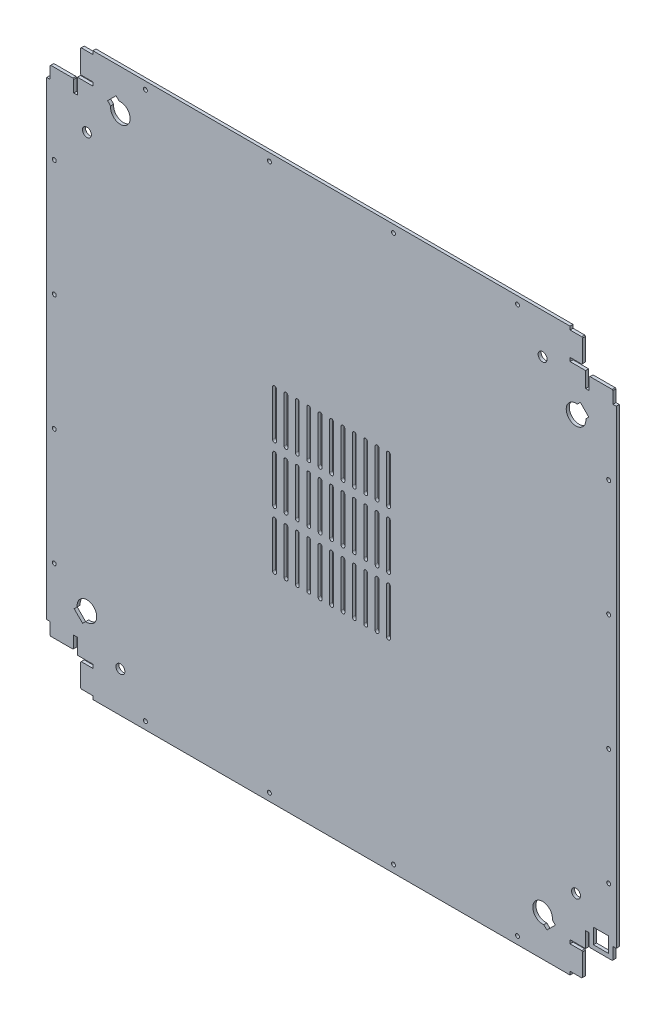
SolidWorks part; units mm, degrees
material "PC Высокая вязкость"
ref_plane "Спереди" through (0, 0, 0) normal (0, 0, 1) x (1, 0, 0)
ref_plane "Сверху" through (0, 0, 0) normal (0, 1, 0) x (1, 0, 0)
ref_plane "Справа" through (0, 0, 0) normal (1, 0, 0) x (0, 0, -1)
sketch "Эскиз1" plane through (0, 0, 0) normal (0, 0, 1) x (1, 0, 0)
  line L1 (375, -370) -> (-375, -370)
  line L2 (375, -370) -> (375, 370)
  line L3 (375, 370) -> (-375, 370)
  line L4 (-375, -370) -> (-375, 370)
  point P1 (375, 0)
  point P2 (0, 370)
  dimension "D1" = 740
  dimension "D2" = 750
extrude "Бобышка-Вытянуть1" add sketch "Эскиз1" along normal blind 4
sketch "Эскиз11" plane through (0, 0, 4) normal (0, 0, 1) x (1, 0, 0)
  line L0 (-375, 370) -> (-375, -370) construction
  line L1 (-375, -370) -> (375, -370) construction
  line L2 (-365, -240) -> (-365, -86.67) construction
  line L3 (-245, -360) -> (-81.67, -360) construction
  line L4 (-375, 370) -> (-375, -370) construction
  line L5 (0, 0) -> (0, 50000) construction
  line L6 (0, 0) -> (-50000, 0) construction
  line L9 (0, 0) -> (50000, 0) construction
  line L10 (365, -240) -> (365, -86.67) construction
  circle A0 centre (-365, -240) radius 2.6
  circle A10 centre (-245, -360) radius 2.6
  circle A25 centre (-365, -86.67) radius 2.6
  circle A26 centre (-365, 66.66) radius 2.6
  circle A27 centre (-365, 219.99) radius 2.6
  circle A28 centre (-81.67, -360) radius 2.6
  circle A29 centre (81.66, -360) radius 2.6
  circle A30 centre (244.99, -360) radius 2.6
  circle A31 centre (365, 219.99) radius 2.6
  circle A32 centre (365, 66.66) radius 2.6
  circle A33 centre (365, -86.67) radius 2.6
  circle A34 centre (365, -240) radius 2.6
  circle A35 centre (-245, 360) radius 2.6
  circle A36 centre (-81.67, 360) radius 2.6
  circle A37 centre (81.66, 360) radius 2.6
  circle A38 centre (244.99, 360) radius 2.6
  dimension "D1" = 5.2
  dimension "D3" = 130
  dimension "D6" = 10
  dimension "D2" = 10
  dimension "D5" = 153.33
  dimension "D7" = 130
  dimension "D9" = 163.33
  dimension "D4" = 4
  dimension "D8" = 4
extrude "Вырез-Вытянуть4" cut sketch "Эскиз11" against normal through all
sketch "Эскиз6" plane through (0, 0, 4) normal (0, 0, 1) x (1, 0, 0)
  line L0 (0, 5) -> (375, -370) construction
  line L1 (-375, -370) -> (375, -370) construction
  line L2 (375, -370) -> (375, 370) construction
  line L3 (-375, -370) -> (0, 5) construction
  line L7 (-375, 370) -> (-5, 0) construction
  line L8 (-5, 0) -> (-375, -370) construction
  circle A0 centre (0, 5) radius 530.3301 construction
  circle A1 centre (265, -360) radius 2.75 construction
  circle A3 centre (-5, 0) radius 523.259 construction
  point P0 (0, 5)
  point P1 (-5, 0)
  point P11 (-375, -370)
  dimension "D3" = 1060.6602
  dimension "D4" = 5.5
  dimension "D11" = 1046.518
  dimension "D1" = 0
  dimension "D2" = 5
  dimension "D5" = 10
  dimension "D6" = 110
  dimension "D7" = 90
  dimension "D12" = 90
  dimension "D13" = 5
sketch "Эскиз9" plane through (0, 0, 4) normal (0, 0, 1) x (1, 0, 0)
  line L55 (-375, -309.1) -> (-370.6, -309.1)
  line L56 (-375, 370) -> (-375, -370) construction
  line L57 (-370.6, -309.1) -> (-370.6, -324.6)
  line L58 (-369.6, -325.6) -> (-340.4, -325.6)
  line L59 (-339.4, -324.6) -> (-339.4, -309.1)
  line L60 (-339.4, -309.1) -> (-334.6, -309.1)
  line L61 (-334.6, -309.1) -> (-334.6, -329.6)
  line L62 (-314.1, -370) -> (-314.1, -365.6)
  line L63 (-375, -370) -> (375, -370) construction
  line L64 (-314.1, -365.6) -> (-329.6, -365.6)
  line L65 (-330.6, -364.6) -> (-330.6, -335.4)
  line L66 (-329.6, -334.4) -> (-314.1, -334.4)
  line L67 (-314.1, -334.4) -> (-314.1, -329.6)
  line L68 (-314.1, -329.6) -> (-334.6, -329.6)
  line L71 (-375, 370) -> (-375, -370) construction
  line L72 (-375, -329.5) -> (-337, -329.5) construction
  line L100 (-375, -309.1) -> (-375, -370)
  line L101 (-375, -370) -> (-335, -370) construction
  line L102 (-375, -370) -> (-375, -330) construction
  line L103 (-375, -330) -> (-335, -330) construction
  line L104 (-335, -370) -> (-335, -330) construction
  line L105 (-375, -370) -> (-314.1, -370)
  line L106 (-370.6, -324.6) -> (-369.6, -325.6)
  line L107 (-340.4, -325.6) -> (-339.4, -324.6)
  line L108 (-330.6, -335.4) -> (-329.6, -334.4)
  line L109 (-329.6, -365.6) -> (-330.6, -364.6)
  point P8 (-370.6, -325.6)
  point P9 (-339.4, -325.6)
  point P17 (-330.6, -334.4)
  point P18 (-330.6, -365.6)
  dimension "D2" = 4.4
  dimension "D1" = 40
  dimension "D3" = 4.4
  dimension "D4" = 4.4
  dimension "D5" = 4.8
  dimension "D6" = 16.5
  dimension "D7" = 40.4
  dimension "D8" = 40.4
extrude "Вырез-Вытянуть3" cut sketch "Эскиз9" against normal through all
sketch "Эскиз5" plane through (0, 0, 0) normal (0, 0, -1) x (-1, 0, 0)
  line L0 (314.1, -370) -> (-375, -370) construction
  line L1 (375, 370) -> (375, -309.1) construction
  line L9 (323.625, -285.7972) -> (327.6569, -289.8291)
  line L11 (318.6, -269.6) -> (35673.9391, -35624.9391) construction
  line L13 (278.5162, -316.4838) -> (35633.8552, 35038.8552) construction
  line L14 (327.6569, -289.8291) -> (338.8291, -278.6569)
  line L15 (338.8291, -278.6569) -> (334.7972, -274.625)
  line L21 (327.6569, -289.2635) -> (338.2635, -278.6569) construction
  line L22 (323.7678, -285.3744) -> (327.6569, -289.2635) construction
  line L23 (338.2635, -278.6569) -> (334.3744, -274.7678) construction
  line L47 (265.1, -329.9) -> (290.9, -304.1) construction
  arc A4 (334.3744, -274.7678) -> (323.7678, -285.3744) centre (322, -273) ccw construction
  arc A5 (334.7972, -274.625) -> (323.625, -285.7972) centre (322, -273) ccw
  circle A6 centre (278, -317) radius 5.9
  circle A8 centre (278, -317) radius 5.5 construction
  point P10 (0, 26.0871)
  dimension "D4" = 5.5
  dimension "D6" = 0.4
  dimension "D7" = 11
  dimension "D5" = 0.4
  dimension "D10" = 12.9
  dimension "D11" = 12.9
  dimension "D14" = 12.9
  dimension "D15" = 12.9
  dimension "D16" = 97
  dimension "D17" = 53
  dimension "D18" = 53
  dimension "D28" = 7.5
  dimension "D29" = 7.5
  dimension "D30" = 15.5
  dimension "D31" = 97
  dimension "D32" = 135
extrude "Вырез-Вытянуть1" cut sketch "Эскиз5" against normal through all
ref_axis "Ось2" through (0, 5, 4) along (0, 0, 1)
ref_axis "Ось3" through (-5, 0, 4) along (0, 0, 1)
ref_axis "Ось4" through (0, 0, 0) along (0, 0, 1)
pattern_circular "Круговой массив2" count 2 every 90 about axis through (0, 5, 4) along (0, 0, 1) of "Вырез-Вытянуть1", "Вырез-Вытянуть3"
pattern_circular "Круговой массив3" count 2 every 90 about axis through (-5, 0, 4) along (0, 0, 1) of "Вырез-Вытянуть1", "Вырез-Вытянуть3" reverse direction yes
pattern_circular "Круговой массив4" count 2 over 360 about axis through (0, 0, 0) along (0, 0, 1) of "Вырез-Вытянуть1", "Вырез-Вытянуть3"
sketch "Эскиз12" plane through (0, 0, 4) normal (0, 0, 1) x (1, 0, 0)
  line L0 (375, -309.1) -> (375, 309.1) construction
  line L1 (365, -300) -> (345, -300)
  line L2 (365, -300) -> (365, -320)
  line L3 (365, -320) -> (345, -320)
  line L4 (345, -300) -> (345, -320)
  line L5 (369.6, -325.6) -> (340.4, -325.6) construction
  dimension "D1" = 20
  dimension "D2" = 10
  dimension "D3" = 5.6
extrude "Вырез-Вытянуть5" cut sketch "Эскиз12" against normal through all
sketch "Эскиз15" plane through (0, 0, 0) normal (0, 0, -1) x (-1, 0, 0)
  line L0 (-72.5, -105) -> (-72.5, -45)
  line L1 (-77.5, -45) -> (-77.5, -105)
  line L2 (-57.5, -105) -> (-57.5, -45)
  line L3 (-62.5, -45) -> (-62.5, -105)
  line L4 (-42.5, -105) -> (-42.5, -45)
  line L5 (-47.5, -45) -> (-47.5, -105)
  line L6 (-27.5, -105) -> (-27.5, -45)
  line L7 (-32.5, -45) -> (-32.5, -105)
  line L8 (-12.5, -105) -> (-12.5, -45)
  line L9 (-17.5, -45) -> (-17.5, -105)
  line L10 (2.5, -105) -> (2.5, -45)
  line L11 (-2.5, -45) -> (-2.5, -105)
  line L12 (17.5, -105) -> (17.5, -45)
  line L13 (12.5, -45) -> (12.5, -105)
  line L14 (32.5, -105) -> (32.5, -45)
  line L15 (27.5, -45) -> (27.5, -105)
  line L16 (47.5, -105) -> (47.5, -45)
  line L17 (42.5, -45) -> (42.5, -105)
  line L18 (62.5, -105) -> (62.5, -45)
  line L19 (57.5, -45) -> (57.5, -105)
  line L20 (77.5, -105) -> (77.5, -45)
  line L21 (72.5, -45) -> (72.5, -105)
  line L22 (-57.5, -30) -> (-57.5, 30)
  line L23 (-62.5, 30) -> (-62.5, -30)
  line L24 (-42.5, -30) -> (-42.5, 30)
  line L25 (-47.5, 30) -> (-47.5, -30)
  line L26 (-27.5, -30) -> (-27.5, 30)
  line L27 (-32.5, 30) -> (-32.5, -30)
  line L28 (-12.5, -30) -> (-12.5, 30)
  line L29 (-17.5, 30) -> (-17.5, -30)
  line L30 (2.5, -30) -> (2.5, 30)
  line L31 (-2.5, 30) -> (-2.5, -30)
  line L32 (17.5, -30) -> (17.5, 30)
  line L33 (12.5, 30) -> (12.5, -30)
  line L34 (32.5, -30) -> (32.5, 30)
  line L35 (27.5, 30) -> (27.5, -30)
  line L36 (47.5, -30) -> (47.5, 30)
  line L37 (42.5, 30) -> (42.5, -30)
  line L38 (62.5, -30) -> (62.5, 30)
  line L39 (57.5, 30) -> (57.5, -30)
  line L40 (77.5, -30) -> (77.5, 30)
  line L41 (72.5, 30) -> (72.5, -30)
  line L42 (-57.5, 45) -> (-57.5, 105)
  line L43 (-62.5, 105) -> (-62.5, 45)
  line L44 (-42.5, 45) -> (-42.5, 105)
  line L45 (-47.5, 105) -> (-47.5, 45)
  line L46 (-27.5, 45) -> (-27.5, 105)
  line L47 (-32.5, 105) -> (-32.5, 45)
  line L48 (-12.5, 45) -> (-12.5, 105)
  line L49 (-17.5, 105) -> (-17.5, 45)
  line L50 (2.5, 45) -> (2.5, 105)
  line L51 (-2.5, 105) -> (-2.5, 45)
  line L52 (17.5, 45) -> (17.5, 105)
  line L53 (12.5, 105) -> (12.5, 45)
  line L54 (32.5, 45) -> (32.5, 105)
  line L55 (27.5, 105) -> (27.5, 45)
  line L56 (47.5, 45) -> (47.5, 105)
  line L57 (42.5, 105) -> (42.5, 45)
  line L58 (62.5, 45) -> (62.5, 105)
  line L59 (57.5, 105) -> (57.5, 45)
  line L60 (77.5, 45) -> (77.5, 105)
  line L61 (72.5, 105) -> (72.5, 45)
  line L62 (-72.5, -30) -> (-72.5, 30)
  line L63 (-77.5, 30) -> (-77.5, -30)
  line L64 (-72.5, 45) -> (-72.5, 105)
  line L65 (-77.5, 105) -> (-77.5, 45)
  line L66 (-72.5, -105) -> (-57.5, -105) construction
  line L67 (-72.5, -105) -> (-72.5, -30) construction
  arc A0 (-77.5, -105) -> (-72.5, -105) centre (-75, -105) ccw
  arc A1 (-72.5, -45) -> (-77.5, -45) centre (-75, -45) ccw
  arc A2 (-57.5, -45) -> (-62.5, -45) centre (-60, -45) ccw
  arc A3 (-62.5, -105) -> (-57.5, -105) centre (-60, -105) ccw
  arc A4 (-42.5, -45) -> (-47.5, -45) centre (-45, -45) ccw
  arc A5 (-47.5, -105) -> (-42.5, -105) centre (-45, -105) ccw
  arc A6 (-27.5, -45) -> (-32.5, -45) centre (-30, -45) ccw
  arc A7 (-32.5, -105) -> (-27.5, -105) centre (-30, -105) ccw
  arc A8 (-12.5, -45) -> (-17.5, -45) centre (-15, -45) ccw
  arc A9 (-17.5, -105) -> (-12.5, -105) centre (-15, -105) ccw
  arc A10 (2.5, -45) -> (-2.5, -45) centre (0, -45) ccw
  arc A11 (-2.5, -105) -> (2.5, -105) centre (0, -105) ccw
  arc A12 (17.5, -45) -> (12.5, -45) centre (15, -45) ccw
  arc A13 (12.5, -105) -> (17.5, -105) centre (15, -105) ccw
  arc A14 (32.5, -45) -> (27.5, -45) centre (30, -45) ccw
  arc A15 (27.5, -105) -> (32.5, -105) centre (30, -105) ccw
  arc A16 (47.5, -45) -> (42.5, -45) centre (45, -45) ccw
  arc A17 (42.5, -105) -> (47.5, -105) centre (45, -105) ccw
  arc A18 (62.5, -45) -> (57.5, -45) centre (60, -45) ccw
  arc A19 (57.5, -105) -> (62.5, -105) centre (60, -105) ccw
  arc A20 (77.5, -45) -> (72.5, -45) centre (75, -45) ccw
  arc A21 (72.5, -105) -> (77.5, -105) centre (75, -105) ccw
  arc A22 (-57.5, 30) -> (-62.5, 30) centre (-60, 30) ccw
  arc A23 (-62.5, -30) -> (-57.5, -30) centre (-60, -30) ccw
  arc A24 (-42.5, 30) -> (-47.5, 30) centre (-45, 30) ccw
  arc A25 (-47.5, -30) -> (-42.5, -30) centre (-45, -30) ccw
  arc A26 (-27.5, 30) -> (-32.5, 30) centre (-30, 30) ccw
  arc A27 (-32.5, -30) -> (-27.5, -30) centre (-30, -30) ccw
  arc A28 (-12.5, 30) -> (-17.5, 30) centre (-15, 30) ccw
  arc A29 (-17.5, -30) -> (-12.5, -30) centre (-15, -30) ccw
  arc A30 (2.5, 30) -> (-2.5, 30) centre (0, 30) ccw
  arc A31 (-2.5, -30) -> (2.5, -30) centre (0, -30) ccw
  arc A32 (17.5, 30) -> (12.5, 30) centre (15, 30) ccw
  arc A33 (12.5, -30) -> (17.5, -30) centre (15, -30) ccw
  arc A34 (32.5, 30) -> (27.5, 30) centre (30, 30) ccw
  arc A35 (27.5, -30) -> (32.5, -30) centre (30, -30) ccw
  arc A36 (47.5, 30) -> (42.5, 30) centre (45, 30) ccw
  arc A37 (42.5, -30) -> (47.5, -30) centre (45, -30) ccw
  arc A38 (62.5, 30) -> (57.5, 30) centre (60, 30) ccw
  arc A39 (57.5, -30) -> (62.5, -30) centre (60, -30) ccw
  arc A40 (77.5, 30) -> (72.5, 30) centre (75, 30) ccw
  arc A41 (72.5, -30) -> (77.5, -30) centre (75, -30) ccw
  arc A42 (-57.5, 105) -> (-62.5, 105) centre (-60, 105) ccw
  arc A43 (-62.5, 45) -> (-57.5, 45) centre (-60, 45) ccw
  arc A44 (-42.5, 105) -> (-47.5, 105) centre (-45, 105) ccw
  arc A45 (-47.5, 45) -> (-42.5, 45) centre (-45, 45) ccw
  arc A46 (-27.5, 105) -> (-32.5, 105) centre (-30, 105) ccw
  arc A47 (-32.5, 45) -> (-27.5, 45) centre (-30, 45) ccw
  arc A48 (-12.5, 105) -> (-17.5, 105) centre (-15, 105) ccw
  arc A49 (-17.5, 45) -> (-12.5, 45) centre (-15, 45) ccw
  arc A50 (2.5, 105) -> (-2.5, 105) centre (0, 105) ccw
  arc A51 (-2.5, 45) -> (2.5, 45) centre (0, 45) ccw
  arc A52 (17.5, 105) -> (12.5, 105) centre (15, 105) ccw
  arc A53 (12.5, 45) -> (17.5, 45) centre (15, 45) ccw
  arc A54 (32.5, 105) -> (27.5, 105) centre (30, 105) ccw
  arc A55 (27.5, 45) -> (32.5, 45) centre (30, 45) ccw
  arc A56 (47.5, 105) -> (42.5, 105) centre (45, 105) ccw
  arc A57 (42.5, 45) -> (47.5, 45) centre (45, 45) ccw
  arc A58 (62.5, 105) -> (57.5, 105) centre (60, 105) ccw
  arc A59 (57.5, 45) -> (62.5, 45) centre (60, 45) ccw
  arc A60 (77.5, 105) -> (72.5, 105) centre (75, 105) ccw
  arc A61 (72.5, 45) -> (77.5, 45) centre (75, 45) ccw
  arc A62 (-72.5, 30) -> (-77.5, 30) centre (-75, 30) ccw
  arc A63 (-77.5, -30) -> (-72.5, -30) centre (-75, -30) ccw
  arc A64 (-72.5, 105) -> (-77.5, 105) centre (-75, 105) ccw
  arc A65 (-77.5, 45) -> (-72.5, 45) centre (-75, 45) ccw
  point P204 (2.5, 0)
  dimension "D1" = 5
  dimension "D2" = 5
  dimension "D3" = 60
  dimension "D4" = 11
  dimension "D6" = 90
  dimension "D7" = 15
  dimension "D8" = 75
  dimension "D5" = 3
extrude "Вырез-Вытянуть7" cut sketch "Эскиз15" against normal through all
